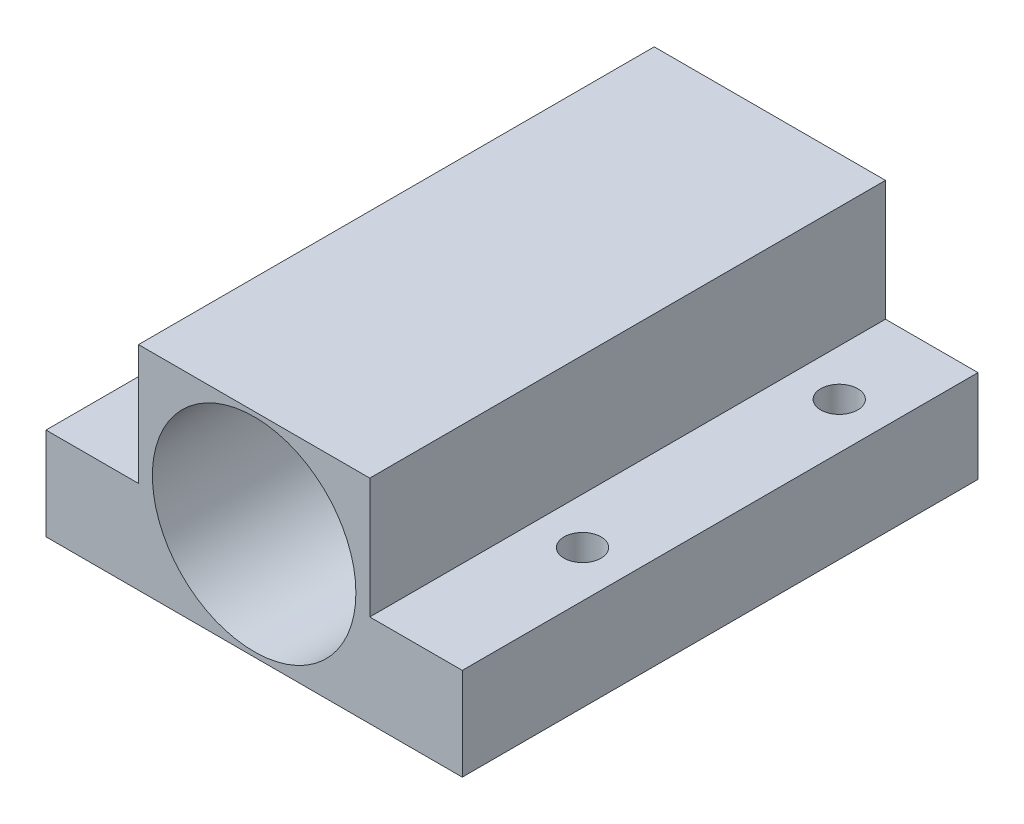
SolidWorks part; units mm, degrees
material "ABS"
ref_plane "Front Plane" through (0, 0, 0) normal (0, 0, 1) x (1, 0, 0)
ref_plane "Top Plane" through (0, 0, 0) normal (0, 1, 0) x (1, 0, 0)
ref_plane "Right Plane" through (0, 0, 0) normal (1, 0, 0) x (0, 0, -1)
sketch "Sketch1" plane through (0, 0, 0) normal (0, 0, 1) x (1, 0, 0)
  line L0 (-65.4098, -16.7) -> (184.5902, -16.7) construction
  line L1 (-12.5, 6.3) -> (12.5, 6.3)
  line L2 (-12.5, 6.3) -> (-12.5, -16.7)
  line L3 (-12.5, -16.7) -> (12.5, -16.7)
  line L4 (12.5, 6.3) -> (12.5, -16.7)
  line L5 (-12.5, 6.3) -> (12.5, -16.7) construction
  line L6 (-12.5, -16.7) -> (12.5, 6.3) construction
  line L7 (12.5, -16.7) -> (22.5, -16.7)
  line L8 (12.5, -16.7) -> (12.5, -6.7)
  line L9 (12.5, -6.7) -> (22.5, -6.7)
  line L10 (22.5, -16.7) -> (22.5, -6.7)
  line L11 (12.5, -16.7) -> (22.5, -6.7) construction
  line L12 (12.5, -6.7) -> (22.5, -16.7) construction
  line L13 (-12.5, -16.7) -> (-22.5, -16.7)
  line L14 (-12.5, -16.7) -> (-12.5, -6.7)
  line L15 (-12.5, -6.7) -> (-22.5, -6.7)
  line L16 (-22.5, -16.7) -> (-22.5, -6.7)
  line L17 (-12.5, -16.7) -> (-22.5, -6.7) construction
  line L18 (-12.5, -6.7) -> (-22.5, -16.7) construction
  circle A0 centre (0, -5.2) radius 4.1
  circle A1 centre (0, -5.2) radius 11
  point P2 (0, 0)
  point P8 (0, -5.2)
  point P14 (17.5, -11.7)
  point P16 (-17.5, -11.7)
  point P19 (0, 0)
  point P20 (0, 0)
  point P21 (0, 0)
  point P22 (0, 0)
  point P26 (0, 0)
  dimension "D4" = 8.2
  dimension "D5" = 22
  dimension "D11" = 11.5
  dimension "D2" = 0
  dimension "D3" = 25
  dimension "D6" = 10
  dimension "D7" = 10
  dimension "D8" = 10
  dimension "D9" = 10
  dimension "D10" = 12.5
  dimension "D12" = 11.5
  dimension "D13" = 5.2
extrude "Boss-Extrude1" add sketch "Sketch1" along normal up to surface (55.75 mm away) contours L4 L1 L2 L3 A1 | L16 L13 L2 L15 | L7 L10 L9 L4 region at (0, 5.9603, 0) region at (-17.5, -11.7, 0) region at (17.5, -11.7, 0)
sketch "Sketch2" plane through (0, -6.7, 0) normal (0, 1, 0) x (1, 0, 0)
  line L0 (-22.5, 0) -> (-12.5, -55.75)
  line L1 (-12.5, -55.75) -> (-22.5, -55.75)
  line L2 (-22.5, -55.75) -> (-12.5, 0)
  line L3 (12.5, 0) -> (22.5, -55.75)
  line L4 (22.5, -55.75) -> (22.5, 0)
  line L5 (22.5, 0) -> (12.5, -55.75)
  circle A0 centre (-17.5, -10) radius 2
  circle A1 centre (17.5, -10) radius 2
  circle A2 centre (17.5, -10) radius 2 construction
  circle A3 centre (-17.5, -10) radius 2 construction
  circle A4 centre (-17.5, -37.75) radius 2
  circle A5 centre (17.5, -37.75) radius 2
  circle A6 centre (17.5, -37.75) radius 2 construction
  circle A7 centre (-17.5, -37.75) radius 2 construction
  dimension "D1" = 4
  dimension "D2" = 4
extrude "Cut-Extrude1" cut sketch "Sketch2" against normal blind 9 contours A0 | A4 | A1 | A5
